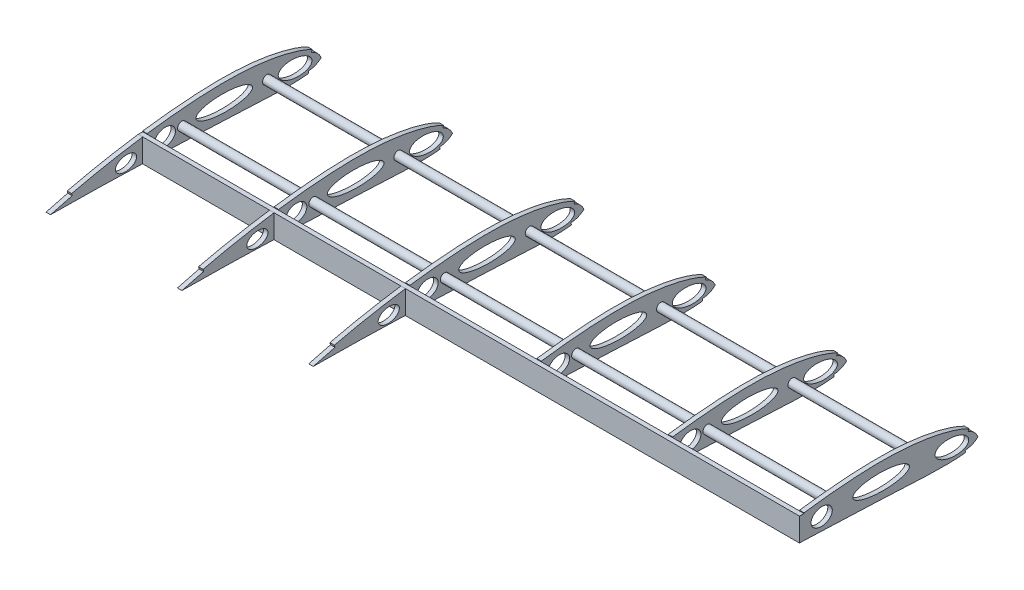
SolidWorks part; units mm, degrees
ref_plane "Front Plane" through (0, 0, 0) normal (0, 0, 1) x (1, 0, 0)
ref_plane "Top Plane" through (0, 0, 0) normal (0, 1, 0) x (1, 0, 0)
ref_plane "Right Plane" through (0, 0, 0) normal (1, 0, 0) x (0, 0, -1)
curve "Curve1"
  spline degree 3 poles (0, 0.2561, 197) (0, 1.149, 193.7201) (0, 2.9304, 187.176) (0, 6.1695, 174.0663) (0, 9.7483, 157.6722) (0, 13.2762, 137.9533) (0, 16.1679, 118.2496) (0, 18.2306, 98.5349) (0, 19.5171, 78.822) (0, 19.5301, 62.3654) (0, 18.621, 49.2257) (0, 17.4237, 39.3576) (0, 15.6579, 29.4682) (0, 13.5343, 21.2733) (0, 11.3895, 14.7062) (0, 9.3648, 9.7544) (0, 7.1751, 5.5294) (0, 4.5558, 1.862) (0, 0.3432, -1.3305) (0, -2.8786, 2.1154) (0, -4.1432, 5.6315) (0, -4.9968, 9.819) (0, -5.4308, 14.7645) (0, -5.7379, 21.3389) (0, -5.7149, 29.5521) (0, -5.4392, 39.4043) (0, -4.9143, 49.2495) (0, -4.3, 62.3829) (0, -3.5118, 78.7969) (0, -2.7716, 98.5006) (0, -1.9498, 118.198) (0, -1.2497, 137.8972) (0, -0.7348, 157.5981) (0, -0.4734, 174.0162) (0, -0.3012, 187.1497) (0, -0.2711, 193.7166) (0, -0.2561, 197) knots 0 0 0 0 0.025305 0.050488 0.10052 0.150191 0.199587 0.24874 0.297716 0.346601 0.371103 0.395726 0.42057 0.445825 0.458702 0.47192 0.485786 0.493461 0.506863 0.516148 0.522766 0.535269 0.547551 0.559786 0.584229 0.608681 0.633151 0.657622 0.706558 0.755482 0.804406 0.85332 0.902221 0.951113 0.975557 1 1 1 1
sketch "Sketch2" plane through (0, 0, 0) normal (1, 0, 0) x (0, 0, -1)
  line L0 (-197, 0.2561) -> (-197, -0.2561)
  line L1 (-197, 0) -> (0, 0) construction
  line L2 (-40, 17.4248) -> (-40, -5.373) construction
  line L3 (-100, 17.9747) -> (-100, -2.6983) construction
  line L4 (0, 0) -> (-40, 6.0259) construction
  line L5 (-40, 6.0259) -> (-100, 7.6382) construction
  line L6 (-100, 7.6382) -> (-197, 0) construction
  line L8 (-124.4398, 15.2116) -> (-124.4398, -1.7354)
  line L11 (-124.4398, 15.2116) -> (-127.6098, 15.2116)
  line L12 (-124.4398, 15.2116) -> (-124.4398, 8.8616)
  line L13 (-124.4398, 8.8616) -> (-127.6098, 8.8616)
  line L14 (-127.6098, 15.2116) -> (-127.6098, 8.8616)
  circle A0 centre (-100, 7.6382) radius 3
  circle A1 centre (-40, 6.0259) radius 3
  ellipse E0 centre (-70, 6.8321) end of major axis (-50.0072, 6.2948) minor radius 6.0022
  ellipse E1 centre (-20, 3.013) end of major axis (-31.8661, 4.8006) minor radius 6
  ellipse E2 centre (-111.963, 6.6962) end of major axis (-104.4861, 7.285) minor radius 6
  ellipse E3 centre (-139.3781, 4.5374) end of major axis (-131.9012, 5.1262) minor radius 5
  spline S0 degree 3 poles (-2505.0904, 6578.1919) (-527.861, -219.0758) (-371.1571, -42.5272) (-174.0663, 6.1695) (-157.6722, 9.7483) (-137.9533, 13.2762) (-118.2496, 16.1679) (-98.5349, 18.2306) (-78.822, 19.5171) (-62.3654, 19.5301) (-49.2257, 18.621) (-39.3576, 17.4237) (-29.4682, 15.6579) (-21.2733, 13.5343) (-14.7062, 11.3895) (-9.7544, 9.3648) (-5.5294, 7.1751) (-1.862, 4.5558) (1.3305, 0.3432) (-2.1154, -2.8786) (-5.6315, -4.1432) (-9.819, -4.9968) (-14.7645, -5.4308) (-21.3389, -5.7379) (-29.5521, -5.7149) (-39.4043, -5.4392) (-49.2495, -4.9143) (-62.3829, -4.3) (-78.7969, -3.5118) (-98.5006, -2.7716) (-118.198, -1.9498) (-137.8972, -1.2497) (-157.5981, -0.7348) (-174.0162, -0.4734) (-446.5443, 3.0993) (-713.3068, -85.3082) (-915.0044, 6909.6127) knots -1.410705 -1.410705 -1.410705 -1.410705 0.025305 0.050488 0.10052 0.150191 0.199587 0.24874 0.297716 0.346601 0.371103 0.395726 0.42057 0.445825 0.458702 0.47192 0.485786 0.493461 0.506863 0.516148 0.522766 0.535269 0.547551 0.559786 0.584229 0.608681 0.633151 0.657622 0.706558 0.755482 0.804406 0.85332 0.902221 0.951113 0.975557 2.931183 2.931183 2.931183 2.931183 only from (-197, 0.2561) to (-197, -0.2561) construction
  spline S1 degree 3 poles (-197, 0.2561) (-193.7201, 1.149) (-187.176, 2.9304) (-174.0663, 6.1695) (-157.6722, 9.7483) (-137.9533, 13.2762) (-118.2496, 16.1679) (-98.5349, 18.2306) (-78.822, 19.5171) (-62.3654, 19.5301) (-49.2257, 18.621) (-39.3576, 17.4237) (-29.4682, 15.6579) (-21.2733, 13.5343) (-14.7062, 11.3895) (-9.7544, 9.3648) (-5.5294, 7.1751) (-1.862, 4.5558) (1.3305, 0.3432) (-2.1154, -2.8786) (-5.6315, -4.1432) (-9.819, -4.9968) (-14.7645, -5.4308) (-21.3389, -5.7379) (-29.5521, -5.7149) (-39.4043, -5.4392) (-49.2495, -4.9143) (-62.3829, -4.3) (-78.7969, -3.5118) (-98.5006, -2.7716) (-118.198, -1.9498) (-137.8972, -1.2497) (-157.5981, -0.7348) (-174.0162, -0.4734) (-187.1497, -0.3012) (-193.7166, -0.2711) (-197, -0.2561) knots 0 0 0 0 0.025305 0.050488 0.10052 0.150191 0.199587 0.24874 0.297716 0.346601 0.371103 0.395726 0.42057 0.445825 0.458702 0.47192 0.485786 0.493461 0.506863 0.516148 0.522766 0.535269 0.547551 0.559786 0.584229 0.608681 0.633151 0.657622 0.706558 0.755482 0.804406 0.85332 0.902221 0.951113 0.975557 1 1 1 1
  dimension "D3" = 6
  dimension "D4" = 6
  dimension "D12" = 5
  dimension "D13" = 3.17
  dimension "D17" = 15
  dimension "D1" = 40
  dimension "D2" = 60
  dimension "D5" = 40
  dimension "D6" = 12
  dimension "D7" = 12
  dimension "D8" = 15
  dimension "D9" = 12
  dimension "D10" = 24
  dimension "D11" = 12
  dimension "D15" = 20
  dimension "D16" = 10
  dimension "D14" = 6.35
extrude "Spars" add sketch "Sketch2" along normal blind 467 contours A1 | A0
extrude "Base Wing" add sketch "Sketch2<9>" along normal blind 3.175 contours A0 | E0 | A1 | E2 | E1 | S1 L0 | E3
sketch "Sketch2<9>" plane through (0, 0, 0) normal (1, 0, 0) x (0, 0, -1) same geometry as "Sketch2"
sketch "Sketch3" plane through (3.175, 0, 0) normal (1, 0, 0) x (0, 0, -1)
  line L0 (-197.1241, 0.224) -> (-177.7605, 5.2292)
  line L1 (-177.7605, 5.2292) -> (-197.1241, 0.224) construction
  line L2 (-177.7605, 5.2292) -> (-177.3632, 3.6922) construction
  line L3 (-197.1241, 0.224) -> (-196.7268, -1.313) construction
  line L4 (-177.3632, 3.6922) -> (-196.7268, -1.313) construction
  line L5 (0, 0) -> (-1.5698, 0.2365) construction
  line L6 (0, 0) -> (-40, 6.0259) construction
  line L7 (-7.8655, 8.3531) -> (-8.591, 6.9411)
  line L8 (-4.3591, 4.3441) -> (-3.3767, 5.5912) construction
  line L9 (-8.591, 6.9411) -> (-4.3591, 4.3441) construction
  line L10 (-4.3591, 4.3441) -> (-1.5698, 0.2365) construction
  line L11 (-5.3287, -3.9604) -> (-5.7651, -2.434) construction
  line L12 (-10.4332, -4.9861) -> (-10.6411, -3.4123)
  line L13 (-3.3767, 5.5912) -> (-2.3943, 6.8382)
  line L14 (-1.5698, 0.2365) -> (-5.7651, -2.434) construction
  line L15 (-10.6411, -3.4123) -> (-5.7651, -2.434) construction
  line L16 (0, 0) -> (1.5698, -0.2365)
  line L17 (-5.3287, -3.9604) -> (-4.8922, -5.4867)
  line L18 (-197.1241, 0.224) -> (-177.7605, 5.2292) construction
  line L23 (-197.1241, 0.224) -> (-197.5214, 1.761) construction
  line L24 (-177.7605, 5.2292) -> (-178.1578, 6.7662) construction
  line L25 (-197.5214, 1.761) -> (-178.1578, 6.7662) construction
  line L26 (-197.5214, 1.761) -> (-196.7268, -1.313)
  line L27 (-197.5214, 1.761) -> (-178.1578, 6.7662)
  line L28 (-196.7268, -1.313) -> (-177.3632, 3.6922)
  line L29 (-178.1578, 6.7662) -> (-177.3632, 3.6922)
  spline S0 degree 3 poles (-197, 0.2561) (-193.7201, 1.149) (-187.176, 2.9304) (-174.0663, 6.1695) (-157.6722, 9.7483) (-137.9533, 13.2762) (-118.2496, 16.1679) (-98.5349, 18.2306) (-78.822, 19.5171) (-62.3654, 19.5301) (-49.2257, 18.621) (-39.3576, 17.4237) (-29.4682, 15.6579) (-21.2733, 13.5343) (-14.7062, 11.3895) (-9.7544, 9.3648) (-5.5294, 7.1751) (-1.862, 4.5558) (1.3305, 0.3432) (-2.1154, -2.8786) (-5.6315, -4.1432) (-9.819, -4.9968) (-14.7645, -5.4308) (-21.3389, -5.7379) (-29.5521, -5.7149) (-39.4043, -5.4392) (-49.2495, -4.9143) (-62.3829, -4.3) (-78.7969, -3.5118) (-98.5006, -2.7716) (-118.198, -1.9498) (-137.8972, -1.2497) (-157.5981, -0.7348) (-174.0162, -0.4734) (-187.1497, -0.3012) (-193.7166, -0.2711) (-197, -0.2561) knots 0 0 0 0 0.025305 0.050488 0.10052 0.150191 0.199587 0.24874 0.297716 0.346601 0.371103 0.395726 0.42057 0.445825 0.458702 0.47192 0.485786 0.493461 0.506863 0.516148 0.522766 0.535269 0.547551 0.559786 0.584229 0.608681 0.633151 0.657622 0.706558 0.755482 0.804406 0.85332 0.902221 0.951113 0.975557 1 1 1 1 construction
  spline S1 degree 2 poles (-8.591, 6.9411) (-3.6378, 5.0995) (-1.5698, 0.2365) knots 0 0 0 1 1 1
  spline S2 degree 2 poles (-10.6411, -3.4123) (-5.4248, -3.2802) (-1.5698, 0.2365) knots 0 0 0 1 1 1
  spline S3 degree 3 poles (-7.8655, 8.3531) (-3.7436, 9.3316) (8.4481, -1.5787) (-6.8965, -7.2435) (-10.4332, -4.9861) knots 0 0 0 0 0.49814 1 1 1 1
  point P5 (-7.8655, 8.3531)
  point P25 (-10.4332, -4.9861)
  point P26 (-5.3287, -3.9604)
  point P27 (0, 0)
  dimension "D6" = 10
  dimension "D4" = 10
  dimension "D1" = 1.5875
  dimension "D2" = 20
  dimension "D3" = 1.5875
  dimension "D5" = 1.5875
pattern_linear "LPattern7" count 3 spacing 92.765 along (1, 0, 0) of "Base Wing"
extrude "Trailing Edge" cut sketch "Sketch3" against normal blind 3.175 contours L27 L29 L28 L26
extrude "Leading Edge" cut sketch "Sketch3<8>" against normal blind 3.175 contours S3 L12 S2 S1 L7
sketch "Sketch3<8>" plane through (3.175, 0, 0) normal (1, 0, 0) x (0, 0, -1) same geometry as "Sketch3"
pattern_linear "LPattern8" count 3 spacing 92.765 along (1, 0, 0) of "Trailing Edge", "Leading Edge"
extrude "Face" cut sketch "Sketch2<10>" along normal blind 3.175 contours L11 L14 L13 L12
sketch "Sketch2<10>" plane through (0, 0, 0) normal (1, 0, 0) x (0, 0, -1) same geometry as "Sketch2"
pattern_linear "LPattern9" count 3 spacing 92.765 along (1, 0, 0) of "Face"
ref_plane "SparPlane" through (0, 0, 127.6098) normal (0, 0, -1) x (-1, 0, 0)
sketch "Sketch12" plane through (0, 0, 127.6098) normal (0, 0, -1) x (-1, 0, 0)
  line L0 (0, 14.7629) -> (0, 8.8616)
  line L1 (0, 8.8616) -> (-3.175, 8.8616)
  line L2 (-3.175, 8.8616) -> (-3.175, -1.7384)
  line L3 (0, 14.7629) -> (-467, 14.7629)
  line L4 (-3.175, -1.7384) -> (-92.765, -1.7384)
  line L5 (-92.765, -1.7384) -> (-92.765, 8.8616)
  line L6 (-92.765, 8.8616) -> (-95.94, 8.8616)
  line L7 (-95.94, 8.8616) -> (-95.94, -1.7384)
  line L8 (-95.94, -1.7384) -> (-185.53, -1.7384)
  line L9 (-185.53, -1.7384) -> (-185.53, 8.8616)
  line L10 (-185.53, 8.8616) -> (-188.705, 8.8616)
  line L11 (-188.705, 8.8616) -> (-188.705, -1.7384)
  line L14 (-188.705, -1.7384) -> (-278.295, -1.7384)
  line L15 (-278.295, -1.7384) -> (-278.295, 8.8616)
  line L16 (-278.295, 8.8616) -> (-281.47, 8.8616)
  line L17 (-281.47, 8.8616) -> (-281.47, -1.7384)
  line L18 (-281.47, -1.7384) -> (-371.06, -1.7384)
  line L19 (-371.06, -1.7384) -> (-371.06, 8.8616)
  line L20 (-371.06, 8.8616) -> (-374.235, 8.8616)
  line L21 (-374.235, 8.8616) -> (-374.235, -1.7384)
  line L23 (-374.235, -1.7384) -> (-463.825, -1.7384)
  line L24 (-463.825, -1.7384) -> (-463.825, 8.8616)
  line L25 (-463.825, 8.8616) -> (-467, 8.8616)
  line L26 (-467, 8.8616) -> (-467, 14.7629)
  point P4 (-463.825, -2.0679)
  point P30 (0, 0)
  dimension "D1" = 467
  dimension "D2" = 10.6
  dimension "D3" = 92.765
extrude "Balsa Spar" add sketch "Sketch12" along normal blind 3.175 contours L3 L26 L25 L24 L23 L21 L20 L19 L18 L17 L16 L15 L14 L11 L10 L9 L8 L7 L6 L5 L4 L2 L1 L0
ref_plane "Secondary Base Wing" through (278.295, 0, 0) normal (1, 0, 0) x (0, 0, -1)
sketch "Sketch13" plane through (278.295, 0, 0) normal (1, 0, 0) x (0, 0, -1)
  line L0 (-127.6098, 8.8616) -> (-124.4398, 8.8616)
  line L1 (-127.6098, 8.8616) -> (-127.6098, -1.7384)
  line L2 (-127.6098, -1.7384) -> (-124.4348, -1.7356)
  line L3 (-124.4398, 8.8616) -> (-124.4398, 14.7629)
  line L4 (-124.4398, 15.2116) -> (-124.4398, 14.7629)
  line L6 (-124.4398, 14.7629) -> (-124.4348, 14.7629)
  line L7 (-124.4348, 14.7629) -> (-124.4348, -1.7356)
  line L11 (-124.4398, 14.7629) -> (-124.4348, 14.7629)
  line L15 (-124.4398, 14.7629) -> (-124.4398, 8.8616)
  line L16 (-124.4398, 15.2116) -> (-124.4398, 14.7629)
  line L17 (-124.4398, 15.2116) -> (-124.4398, 14.7629)
  line L20 (-10.4332, -4.9861) -> (-10.6411, -3.4123)
  line L21 (-10.4332, -4.9861) -> (-10.6411, -3.4123)
  line L22 (-8.591, 6.9411) -> (-7.8655, 8.3531)
  line L23 (-8.591, 6.9411) -> (-7.8655, 8.3531)
  circle A0 centre (-40, 6.0259) radius 3 construction
  circle A1 centre (-40, 6.0259) radius 3
  circle A2 centre (-100, 7.6382) radius 3 construction
  circle A3 centre (-100, 7.6382) radius 3
  ellipse E0 centre (-111.963, 6.6962) end of major axis (-104.4861, 7.285) minor radius 6 construction
  ellipse E1 centre (-70, 6.8321) end of major axis (-50.0072, 6.2948) minor radius 6.0022 construction
  ellipse E2 centre (-20, 3.013) end of major axis (-8.1339, 1.2254) minor radius 6 construction
  ellipse E3 centre (-111.963, 6.6962) end of major axis (-104.4861, 7.285) minor radius 6
  ellipse E4 centre (-70, 6.8321) end of major axis (-50.0072, 6.2948) minor radius 6.0022
  ellipse E5 centre (-20, 3.013) end of major axis (-8.1339, 1.2254) minor radius 6
  parabola Q2 (-10.6411, -3.4123) -> (-1.5698, 0.2365) focus (-8.21, 3.6444) apex (-5.7651, -2.434)
  parabola Q3 (-10.6411, -3.4123) -> (-1.5698, 0.2365) focus (-8.21, 3.6444) apex (-5.7651, -2.434)
  parabola Q4 (-1.5698, 0.2365) -> (-8.591, 6.9411) focus (-8.2542, 0.2651) apex (-4.3591, 4.3441)
  parabola Q5 (-1.5698, 0.2365) -> (-8.591, 6.9411) focus (-8.2542, 0.2651) apex (-4.3591, 4.3441)
  spline S2 degree 3 poles (-1367.7155, -2590.3642) (-923.6568, -46.7157) (-512.7824, 14.5145) (-98.5006, -2.7716) (-78.7969, -3.5118) (-62.3829, -4.3) (-49.2495, -4.9143) (-39.4043, -5.4392) (-29.5521, -5.7149) (-21.3389, -5.7379) (43.0686, -2.729) (98.3082, 46.1829) (278.6729, 2978.1004) knots -2.436694 -2.436694 -2.436694 -2.436694 0.552208 0.601132 0.650055 0.698992 0.723462 0.747933 0.772385 0.796827 0.809062 1.252024 1.252024 1.252024 1.252024 only from (-124.4348, -1.7356) to (-10.4332, -4.9861)
  spline S3 degree 3 poles (-2916.9485, -710.3536) (73.3325, -105.9441) (37.3308, -9.8882) (-14.7062, 11.3895) (-21.2733, 13.5343) (-29.4682, 15.6579) (-39.3576, 17.4237) (-49.2257, 18.621) (-62.3654, 19.5301) (-78.822, 19.5171) (-98.5349, 18.2306) (-428.5049, -16.293) (-710.2974, -378.6878) (-1008.0238, 2779.7932) knots -0.204448 -0.204448 -0.204448 -0.204448 0.1894 0.202617 0.215494 0.240749 0.265593 0.290217 0.314719 0.363604 0.412579 0.461733 2.832769 2.832769 2.832769 2.832769 only from (-7.8655, 8.3531) to (-124.4398, 15.2116)
  spline S4 degree 3 poles (-124.4348, -1.7356) (-122.3565, -1.8115) (-113.7109, -2.137) (-98.5006, -2.7716) (-78.7969, -3.5118) (-62.3829, -4.3) (-49.2495, -4.9143) (-39.4043, -5.4392) (-29.5521, -5.7149) (-21.3389, -5.7379) (-14.96, -5.4399) (-11.8784, -5.177) (-10.4332, -4.9861) knots 0.536725 0.536725 0.536725 0.536725 0.552208 0.601132 0.650055 0.698992 0.723462 0.747933 0.772385 0.796827 0.809062 0.819888 0.819888 0.819888 0.819888
  spline S5 degree 3 poles (-7.8655, 8.3531) (-8.5192, 8.689) (-10.7997, 9.7922) (-14.7062, 11.3895) (-21.2733, 13.5343) (-29.4682, 15.6579) (-39.3576, 17.4237) (-49.2257, 18.621) (-62.3654, 19.5301) (-78.822, 19.5171) (-98.5349, 18.2306) (-113.7356, 16.6402) (-122.3616, 15.4993) (-124.4398, 15.2116) knots 0.183969 0.183969 0.183969 0.183969 0.1894 0.202617 0.215494 0.240749 0.265593 0.290217 0.314719 0.363604 0.412579 0.461733 0.477351 0.477351 0.477351 0.477351
  point P0 (-127.6098, -1.7356)
  point P14 (-124.4398, 15.1006)
  point P62 (0, 0)
  point P63 (0, 0)
  point P64 (-124.4398, 14.4512)
  point P65 (-124.4398, 14.7389)
  dimension "D1" = 0
extrude "Boss-Extrude3" add sketch "Sketch13" along normal blind 3.175 contours L3 L0 L1 L2 S4 L21 Q3 Q5 L23 S5 L17 | E4 | E3 | E5 | A1 | A3
pattern_linear "LPattern11" count 3 spacing 92.765 along (1, 0, 0) of "Boss-Extrude3"
